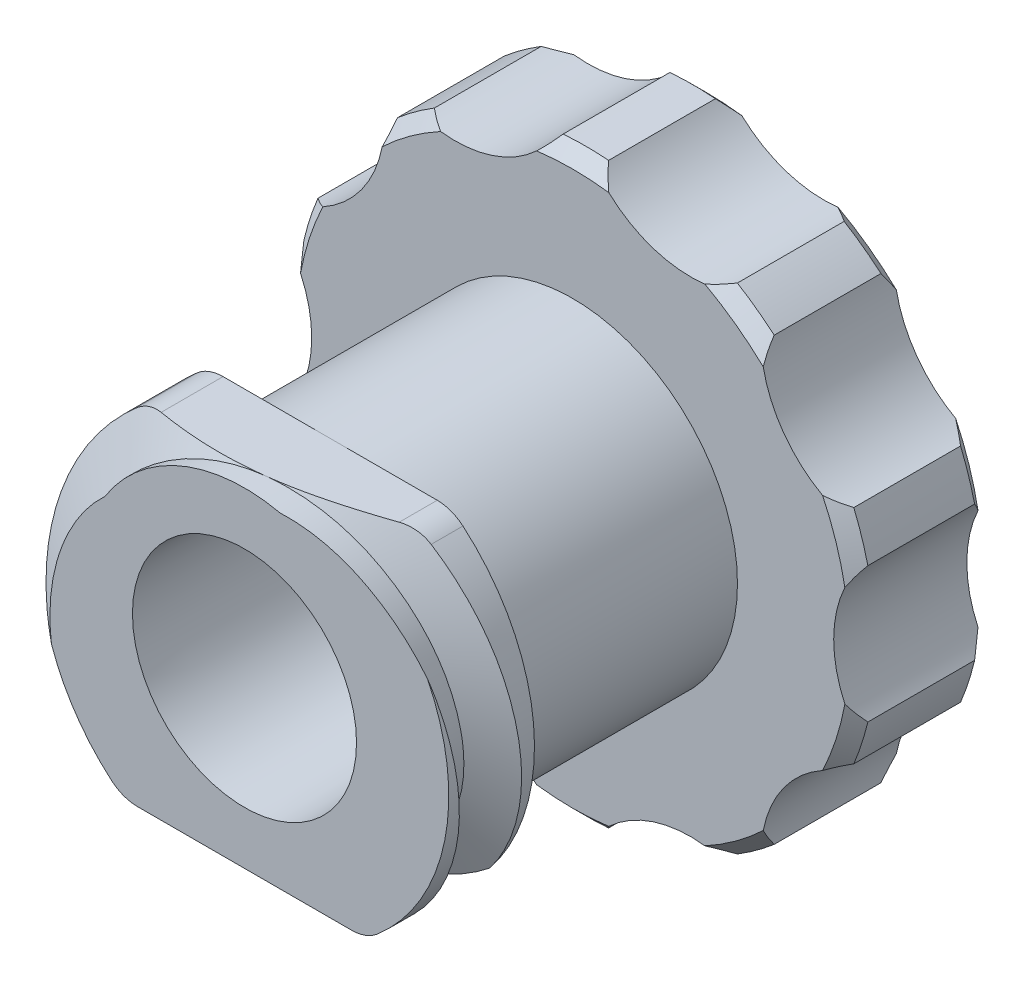
SolidWorks part; units mm, degrees
ref_plane "Front Plane" through (0, 0, 0) normal (0, 0, 1) x (1, 0, 0)
ref_plane "Top Plane" through (0, 0, 0) normal (0, 1, 0) x (1, 0, 0)
ref_plane "Right Plane" through (0, 0, 0) normal (1, 0, 0) x (0, 0, -1)
sketch "Sketch20" plane through (0, 0, 0) normal (0, 0, 1) x (1, 0, 0)
  circle A0 centre (0, 0) radius 3.8171
  arc A1 (-2.9197, 4.7646) -> (-0.4384, 5.5708) centre (-2.2668, 6.9763) ccw
  arc A2 (-2.9197, 4.7646) -> (-3.6291, 4.2491) centre (0, 0) ccw
  arc A3 (-5.1626, 2.1384) -> (-3.6291, 4.2491) centre (-5.9344, 4.3116) ccw
  arc A4 (-5.1626, 2.1384) -> (-5.4336, 1.3045) centre (0, 0) ccw
  arc A5 (-5.4336, -1.3045) -> (-5.4336, 1.3045) centre (-7.3354, 0) ccw
  arc A6 (-5.4336, -1.3045) -> (-5.1626, -2.1384) centre (0, 0) ccw
  arc A7 (-3.6291, -4.2491) -> (-5.1626, -2.1384) centre (-5.9344, -4.3116) ccw
  arc A8 (-3.6291, -4.2491) -> (-2.9197, -4.7646) centre (0, 0) ccw
  arc A9 (-0.4384, -5.5708) -> (-2.9197, -4.7646) centre (-2.2668, -6.9763) ccw
  arc A10 (-0.4384, -5.5708) -> (0.4384, -5.5708) centre (0, 0) ccw
  arc A11 (2.9197, -4.7646) -> (0.4384, -5.5708) centre (2.2668, -6.9763) ccw
  arc A12 (2.9197, -4.7646) -> (3.6291, -4.2491) centre (0, 0) ccw
  arc A13 (5.1626, -2.1384) -> (3.6291, -4.2491) centre (5.9344, -4.3116) ccw
  arc A14 (5.1626, -2.1384) -> (5.4336, -1.3045) centre (0, 0) ccw
  arc A15 (5.4336, 1.3045) -> (5.4336, -1.3045) centre (7.3354, 0) ccw
  arc A16 (5.4336, 1.3045) -> (5.1626, 2.1384) centre (0, 0) ccw
  arc A17 (3.6291, 4.2491) -> (5.1626, 2.1384) centre (5.9344, 4.3116) ccw
  arc A18 (3.6291, 4.2491) -> (2.9197, 4.7646) centre (0, 0) ccw
  arc A19 (0.4384, 5.5708) -> (2.9197, 4.7646) centre (2.2668, 6.9763) ccw
  arc A20 (0.4384, 5.5708) -> (-0.4384, 5.5708) centre (0, 0) ccw
  circle A21 centre (0, 0) radius 5.588 construction
  dimension "D1" = 7.6341
  dimension "D2" = 11.176
extrude "Boss-Extrude1" add sketch "Sketch20" along normal mid plane 2.5654
sketch "Sketch21" plane through (0, 0, -1.2827) normal (0, 0, -1) x (-1, 0, 0)
  arc A20 (3.6291, 4.2491) -> (2.9197, 4.7646) centre (0, 0) ccw
  arc A21 (0.4384, 5.5708) -> (2.9197, 4.7646) centre (2.2668, 6.9763) ccw
  arc A22 (0.4384, 5.5708) -> (-0.4384, 5.5708) centre (0, 0) ccw
  arc A23 (-2.9197, 4.7646) -> (-0.4384, 5.5708) centre (-2.2668, 6.9763) ccw
  arc A24 (-2.9197, 4.7646) -> (-3.6291, 4.2491) centre (0, 0) ccw
  arc A25 (-5.1626, 2.1384) -> (-3.6291, 4.2491) centre (-5.9344, 4.3116) ccw
  arc A26 (-5.1626, 2.1384) -> (-5.4336, 1.3045) centre (0, 0) ccw
  arc A27 (-5.4336, -1.3045) -> (-5.4336, 1.3045) centre (-7.3354, 0) ccw
  arc A28 (-5.4336, -1.3045) -> (-5.1626, -2.1384) centre (0, 0) ccw
  arc A29 (-3.6291, -4.2491) -> (-5.1626, -2.1384) centre (-5.9344, -4.3116) ccw
  arc A30 (-3.6291, -4.2491) -> (-2.9197, -4.7646) centre (0, 0) ccw
  arc A31 (-0.4384, -5.5708) -> (-2.9197, -4.7646) centre (-2.2668, -6.9763) ccw
  arc A32 (-0.4384, -5.5708) -> (0.4384, -5.5708) centre (0, 0) ccw
  arc A33 (2.9197, -4.7646) -> (0.4384, -5.5708) centre (2.2668, -6.9763) ccw
  arc A34 (2.9197, -4.7646) -> (3.6291, -4.2491) centre (0, 0) ccw
  arc A35 (5.1626, -2.1384) -> (3.6291, -4.2491) centre (5.9344, -4.3116) ccw
  arc A36 (5.1626, -2.1384) -> (5.4336, -1.3045) centre (0, 0) ccw
  arc A37 (5.4336, 1.3045) -> (5.4336, -1.3045) centre (7.3354, 0) ccw
  arc A38 (5.4336, 1.3045) -> (5.1626, 2.1384) centre (0, 0) ccw
  arc A39 (3.6291, 4.2491) -> (5.1626, 2.1384) centre (5.9344, 4.3116) ccw
  arc A40 (3.6291, 4.2491) -> (2.9197, 4.7646) centre (0, 0) ccw
  arc A41 (0.4384, 5.5708) -> (2.9197, 4.7646) centre (2.2668, 6.9763) ccw
  arc A42 (0.4384, 5.5708) -> (-0.4384, 5.5708) centre (0, 0) ccw
  arc A43 (-2.9197, 4.7646) -> (-0.4384, 5.5708) centre (-2.2668, 6.9763) ccw
  arc A44 (-2.9197, 4.7646) -> (-3.6291, 4.2491) centre (0, 0) ccw
  arc A45 (-5.1626, 2.1384) -> (-3.6291, 4.2491) centre (-5.9344, 4.3116) ccw
  arc A46 (-5.1626, 2.1384) -> (-5.4336, 1.3045) centre (0, 0) ccw
  arc A47 (-5.4336, -1.3045) -> (-5.4336, 1.3045) centre (-7.3354, 0) ccw
  arc A48 (-5.4336, -1.3045) -> (-5.1626, -2.1384) centre (0, 0) ccw
  arc A49 (-3.6291, -4.2491) -> (-5.1626, -2.1384) centre (-5.9344, -4.3116) ccw
  arc A50 (-3.6291, -4.2491) -> (-2.9197, -4.7646) centre (0, 0) ccw
  arc A51 (-0.4384, -5.5708) -> (-2.9197, -4.7646) centre (-2.2668, -6.9763) ccw
  arc A52 (-0.4384, -5.5708) -> (0.4384, -5.5708) centre (0, 0) ccw
  arc A53 (2.9197, -4.7646) -> (0.4384, -5.5708) centre (2.2668, -6.9763) ccw
  arc A54 (2.9197, -4.7646) -> (3.6291, -4.2491) centre (0, 0) ccw
  arc A55 (5.1626, -2.1384) -> (3.6291, -4.2491) centre (5.9344, -4.3116) ccw
  arc A56 (5.1626, -2.1384) -> (5.4336, -1.3045) centre (0, 0) ccw
  arc A57 (5.4336, 1.3045) -> (5.4336, -1.3045) centre (7.3354, 0) ccw
  arc A58 (5.4336, 1.3045) -> (5.1626, 2.1384) centre (0, 0) ccw
  arc A59 (3.6291, 4.2491) -> (5.1626, 2.1384) centre (5.9344, 4.3116) ccw
  dimension "D1" = 0
extrude "Boss-Extrude2" add sketch "Sketch21" against normal up to vertex (2.5654 mm away) up to point (-0.4384, 5.5708, 1.2827)
sketch "Sketch23" plane through (0, 0, -1.2827) normal (0, 0, 1) x (1, 0, 0)
  circle A0 centre (0, 0) radius 3.175
  dimension "D1" = 6.35
extrude "Boss-Extrude3" add sketch "Sketch23" along normal blind 8.89
ref_plane "Plane1" through (0, 0, -0.5207) normal (0, 0, -1) x (-1, 0, 0)
sketch "Sketch24" plane through (0, 0, 7.6073) normal (0, 0, 1) x (1, 0, 0)
  circle A0 centre (0, 0) radius 2.159
  dimension "D1" = 4.318
extrude "Cut-Extrude1" cut sketch "Sketch24" against normal up to surface (8.128 mm away) draft 1
sketch "Sketch25" plane through (0, 0, 0) normal (1, 0, 0) x (0, 0, -1)
  line L0 (1.0287, 5.588) -> (1.2827, 5.334)
  line L1 (1.2827, 5.588) -> (-1.2827, 5.588) construction
  line L2 (1.2827, 2.1384) -> (1.2827, 4.2491) construction
  line L3 (1.2827, 5.334) -> (1.2827, 5.588)
  line L5 (1.2827, 5.588) -> (1.0287, 5.588)
  line L6 (0, 5.5708) -> (0, 0) construction
  line L7 (-1.2827, 5.5708) -> (1.2827, 5.5708) construction
  line L8 (-1.2827, 5.588) -> (-1.0287, 5.588)
  line L9 (-1.2827, 5.334) -> (-1.2827, 5.588)
  line L10 (-1.0287, 5.588) -> (-1.2827, 5.334)
  line L11 (0, 0) -> (1.2827, 0) construction
  line L12 (1.2827, -1.3045) -> (1.2827, 1.3045) construction
  dimension "D1" = 45
  dimension "D2" = 0.254
revolve "Cut-Revolve1" cut sketch "Sketch25" angle 360 about L11
sketch "Sketch26" plane through (0, 0, 7.6073) normal (0, 0, 1) x (1, 0, 0)
  circle A0 centre (0, 0) radius 2.159 construction
  circle A1 centre (0, 0) radius 2.159
  circle A2 centre (0, 0) radius 3.937
  dimension "D1" = 7.874
extrude "Boss-Extrude4" add sketch "Sketch26" against normal blind 1.651 separate body
ref_plane "Plane2" through (0, 0, 5.1943) normal (0, 0, -1) x (-1, 0, 0)
sketch "Sketch27" plane through (0, 0, 5.1943) normal (0, 0, -1) x (-1, 0, 0)
  circle A1 centre (0, 0) radius 3.175
  circle A2 centre (0, 0) radius 3.175 construction
curve "Helix/Spiral1" pitch 2.5 height 6.875 turns 2.75
sketch "Sketch28" plane through (0, 0, 0) normal (1, 0, 0) x (0, 0, -1)
  line L0 (-5.905, 4.699) -> (-5.1943, 3.175)
  line L1 (-5.1943, 3.175) -> (-4.705, 3.175)
  line L2 (-4.705, 3.175) -> (-3.9943, 4.699)
  line L3 (-3.9943, 4.699) -> (-5.905, 4.699)
  line L4 (-5.1943, 3.175) -> (-5.1943, 4.699) construction
  line L5 (-4.9496, 3.175) -> (-4.9496, 4.699) construction
  line L6 (-1.2827, 3.175) -> (-7.6073, 3.175) construction
  line L7 (-5.5496, 3.937) -> (-4.3496, 3.937) construction
  line L8 (-7.6073, 3.937) -> (-5.5496, 3.937) construction
  line L9 (-7.6073, 3.937) -> (-7.6073, -3.937) construction
  dimension "D1" = 25
  dimension "D2" = 1.2
sweep "Cut-Sweep1" cut profiles "Sketch28" path "Helix/Spiral1"
sketch "Sketch29" plane through (0, 0, 7.6073) normal (0, 0, 1) x (1, 0, 0)
  line L0 (0, 0) -> (0, -3.175) construction
  line L1 (-7.9952, -3.175) -> (7.9952, -3.175)
  line L2 (-7.9952, -3.175) -> (-7.9952, -19.1655)
  line L3 (-7.9952, -19.1655) -> (7.9952, -19.1655)
  line L4 (7.9952, -3.175) -> (7.9952, -19.1655)
  spline S0 degree 2 poles (-2.9877, -1.0744) (-2.657, -1.9941) (-1.8662, -2.5686) (-1.0316, -3.175) (0, -3.175) (1.0316, -3.175) (1.8662, -2.5686) (2.7008, -1.9623) (3.0196, -0.9811) (3.3384, 0) (3.0196, 0.9811) (2.7008, 1.9623) (1.8662, 2.5686) (1.3345, 2.9549) (0.6931, 3.0984) knots 0.10167 0.10167 0.10167 0.133333 0.133333 0.166667 0.166667 0.2 0.2 0.233333 0.233333 0.266667 0.266667 0.3 0.3 0.32162 0.32162 0.32162 weights 0.995341 0.953509 1 0.951057 1 0.951057 1 0.951057 1 0.951057 1 0.951057 1 0.968255 0.97769 construction
  dimension "D1" = 15.9905
extrude "Cut-Extrude2" cut sketch "Sketch29" against normal blind 2.54
sketch "Sketch30" plane through (0, 0, 5.9563) normal (0, 0, -1) x (-1, 0, 0)
  line L0 (0, 19.05) -> (0, 0) construction
  line L1 (-7.9375, 19.05) -> (7.9375, 19.05)
  line L2 (-7.9375, 19.05) -> (-7.9375, 3.175)
  line L3 (-7.9375, 3.175) -> (7.9375, 3.175)
  line L4 (7.9375, 19.05) -> (7.9375, 3.175)
  circle A0 centre (0, 0) radius 3.175 construction
  dimension "D1" = 15.875
extrude "Cut-Extrude3" cut sketch "Sketch30" against normal blind 2.54
fillet "Fillet1" radius 0.762 4 edges at (-2.3279, -3.175, 7.0776) (2.3279, -3.175, 7.3293) (2.3279, 3.175, 6.2771) (-2.3279, 3.175, 6.5288)
combine bodies "Combine3" operation type add bodies to combine 119 123 parameters "D4"=0.635, "D5"=0.3302
